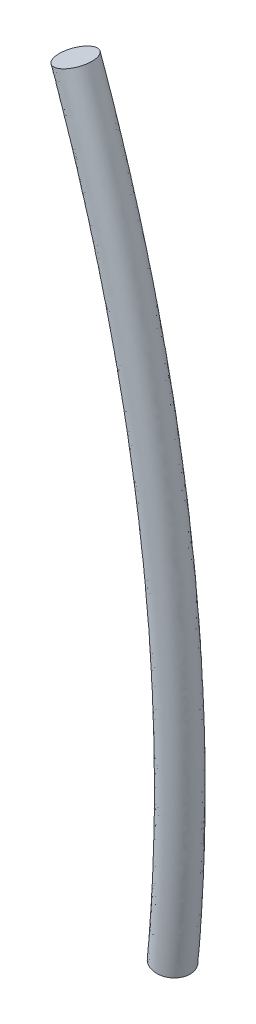
SolidWorks part; units mm, degrees
material "Custom Plastic"
ref_plane "X-Y Datum" through (0, 0, 0) normal (0, 0, 1) x (1, 0, 0)
ref_plane "X-Z Datum" through (0, 0, 0) normal (0, 1, 0) x (1, 0, 0)
ref_plane "Y-Z Datum" through (0, 0, 0) normal (1, 0, 0) x (0, 0, -1)
sketch3d "3DSketch1"
  line L1 (-135.4865, -165.0047, 234.086) -> (-135.4865, -141.5047, 234.086) construction
  circle A2 centre (-150.133, -40.3793, 237.2242) radius 2.286 construction
  spline S0 degree 2 poles (-150.133, -40.3793, 237.2242) (-128.4955, -106.7909, 235.6342) (-136.3601, -173.393, 233.8637) knots 0 0 0 1 1 1
  point P2 (-136.1658, -173.6165, 231.5095)
  point P3 (-136.3601, -173.393, 233.8637)
  point P9 (-150.133, -42.6653, 237.2242)
sweep "Sweep1" add path "3DSketch1" circular profile diameter 6.35 parameters "D3"=6.35
